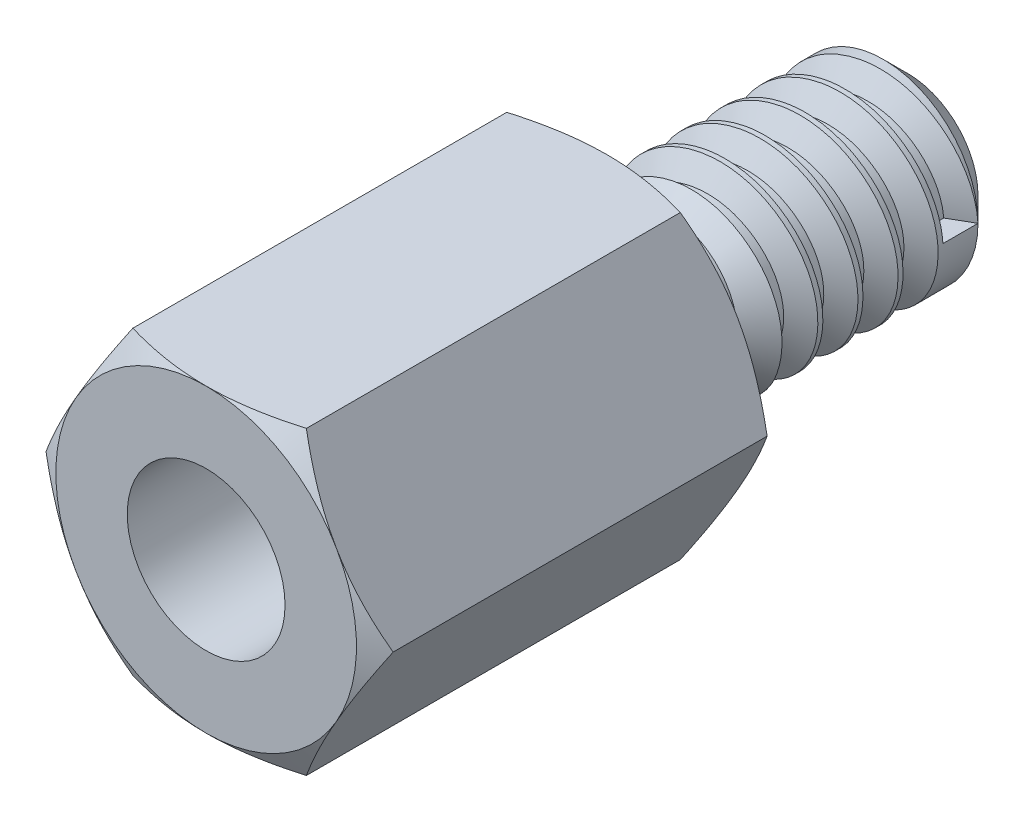
SolidWorks part; units mm, degrees
material "PA Type 6"
ref_plane "Front" through (0, 0, 0) normal (0, 0, 1) x (1, 0, 0)
ref_plane "Top" through (0, 0, 0) normal (0, 1, 0) x (1, 0, 0)
ref_plane "Right" through (0, 0, 0) normal (1, 0, 0) x (0, 0, -1)
sketch "Sketch1" plane through (0, 0, 0) normal (0, 0, 1) x (1, 0, 0)
  line L1 (2.7496, 0) -> (1.3748, 2.3813)
  line L2 (1.3748, 2.3813) -> (-1.3748, 2.3813)
  line L3 (-1.3748, 2.3813) -> (-2.7496, 0)
  line L4 (-2.7496, 0) -> (-1.3748, -2.3813)
  line L5 (-1.3748, -2.3813) -> (1.3748, -2.3813)
  line L6 (1.3748, -2.3813) -> (2.7496, 0)
  circle A0 centre (0, 0) radius 2.3813 construction
  dimension "D1" = 4.7625
extrude "Extrude1" add sketch "Sketch1" along normal mid plane 6.35
sketch "Sketch3" plane through (0, 0, 0) normal (1, 0, 0) x (0, 0, -1)
  line L0 (-3.175, 0) -> (-7.4204, 0) construction
  line L1 (-3.175, 2.3813) -> (-2.2951, 3.9053)
  line L2 (-2.2951, 3.9053) -> (-3.429, 3.9053)
  line L3 (-3.429, 3.9053) -> (-3.429, 2.3813)
  line L4 (-3.429, 2.3813) -> (-3.175, 2.3813)
  line L5 (-3.175, 0) -> (-3.175, 2.3813) construction
  dimension "D1" = 30
  dimension "D2" = 0.254
  dimension "D3" = 1.524
revolve "Cut-Revolve1" cut sketch "Sketch3" angle 360 about L0
mirror "Mirror1" about plane through (0, 0, 0) normal (0, 0, 1) of "Cut-Revolve1"
sketch "Sketch2" plane through (0, 0, 0) normal (1, 0, 0) x (0, 0, -1)
  line L0 (3.175, 0) -> (0, 0) construction
  line L1 (3.175, 1.1151) -> (4.1275, 1.1151)
  line L2 (3.175, 0) -> (3.175, 2.3813) construction
  line L3 (4.1275, 1.1151) -> (4.5124, 1.5)
  line L4 (4.5124, 1.5) -> (7.5526, 1.5)
  line L5 (7.5526, 1.5) -> (7.9375, 1.1151)
  line L6 (7.9375, 1.1151) -> (7.9375, 0)
  line L7 (7.9375, 0) -> (3.175, 0)
  line L8 (3.175, 1.1151) -> (3.175, 0)
  line L9 (3.175, -2.3813) -> (3.175, 0) construction
  dimension "D1" = 2.2301
  dimension "D2" = 3
  dimension "D3" = 0.9525
  dimension "D4" = 4.7625
  dimension "D5" = 45
revolve "M3 stud" add sketch "Sketch2" angle 360 about L0
cosmetic thread "Cosmetic Thread1" parameters "D2"=2.0676
hole_wizard "M3 Tapped Hole" positions "Sketch5" profile "Sketch4" tap size "M3x0.5" standard "ANSI Metric"
sketch "Sketch5" plane through (0, 0, 3.175) normal (0, 0, 1) x (1, 0, 0)
  point P0 (0, 0)
cosmetic thread "Cosmetic Thread2" parameters "D1"=5.9944, "D2"=3
sketch "Sketch4" plane through (0, 0, 3.175) normal (1, 0, 0) x (0, -1, 0)
  line L0 (0, 0) -> (0, 6.7455)
  line L1 (0, 6.7455) -> (1.25, 5.9944)
  line L2 (1.25, 5.9944) -> (1.25, 0)
  line L5 (1.25, 0) -> (0, 0)
  line L10 (0, 6.7455) -> (-1.25, 5.9944) construction
  line L11 (0, -6.35) -> (0, 107.95) construction
  dimension "Tap Drill Dia." = 2.5
  dimension "Tap Drill Depth" = 5.9944
  dimension "Drill Angle" = 118
thread "Thread1" pitch 0.635 method cut profile "Thread Profile1" start angle 0, offset 0, length 0, pitch 0.635, diameter 3
ref_plane "Plane1" through (1.5, 0, -7.5526) normal (0, -1, 0) x (1, 0, 0)
sketch "Thread Profile1" plane through (1.5, 0, -7.5526) normal (0, -1, 0) x (1, 0, 0)
  line L0 (0, 0) -> (0, 0.635) construction
  line L11 (0, 0) -> (0, 0.5556)
  line L12 (0, 0.5556) -> (-0.3437, 0.3572)
  line L13 (-0.3437, 0.3572) -> (-0.3437, 0.1984)
  line L15 (-0.3437, 0.1984) -> (0, 0)
  line L17 (-0.3437, 0.2778) -> (0, 0.2778) construction
  point P2 (0, 0)
  dimension "Pitch" = 0.635
  dimension "Profile_Angle" = 60
  dimension "Profile_Land" = 0.1588
  dimension "Profile_Height" = 0.3437
